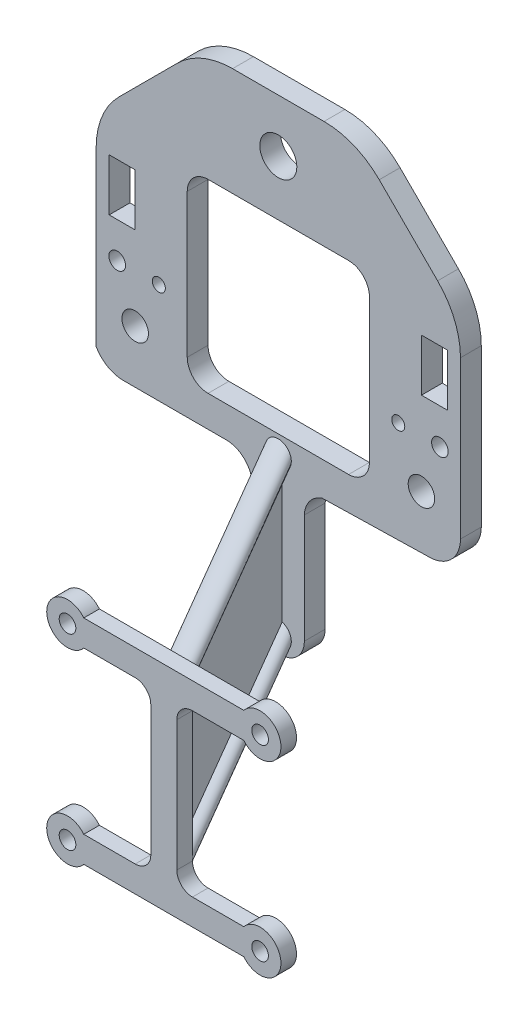
SolidWorks part; units mm, degrees
ref_plane "Спереди" through (0, 0, 0) normal (0, 0, 1) x (1, 0, 0)
ref_plane "Сверху" through (0, 0, 0) normal (0, 1, 0) x (1, 0, 0)
ref_plane "Справа" through (0, 0, 0) normal (1, 0, 0) x (0, 0, -1)
sketch "Model" plane through (0, 0, 0) normal (0, 0, 1) x (1, 0, 0)
  line L0 (-32.5, 1.0025) -> (-27.5, 1.0025)
  line L1 (-27.5, 1.0025) -> (-27.5, 11.0025)
  line L2 (-27.5, 11.0025) -> (-32.5, 11.0025)
  line L3 (-32.5, 11.0025) -> (-32.5, 1.0025)
  line L4 (32.5, 11.0025) -> (27.5, 11.0025)
  line L5 (27.5, 11.0025) -> (27.5, 1.0025)
  line L6 (27.5, 1.0025) -> (32.5, 1.0025)
  line L7 (32.5, 1.0025) -> (32.5, 11.0025)
  line L8 (-8.7868, 37.1928) -> (8.7868, 37.1928)
  line L9 (35, 10.9796) -> (35, -19.1878)
  line L10 (-29.7898, -25.1878) -> (-10, -25.1878)
  line L11 (5, -30.1878) -> (5, -51.1878)
  line L12 (0.5, -55.6878) -> (-0.5, -55.6878)
  line L13 (-5, -51.1878) -> (-5, -30.1878)
  line L14 (8.4254, -25.669) -> (29, -25.1878)
  line L15 (-35, -22.1633) -> (-35, 10.9796)
  line L16 (-15.452, -19.1878) -> (15.452, -19.1878)
  line L17 (-17.5, -3.7682) -> (-17.5, -19.1878) construction
  line L18 (-17.5, -19.1878) -> (-15.452, -19.1878) construction
  line L19 (17.5, 14.8517) -> (17.5, 16.4118) construction
  line L20 (-27.5, 27.0083) -> (27.5, 27.0083) construction
  line L21 (17.5, 16.4118) -> (11.2964, 16.4118) construction
  line L22 (-27.5, 27.0083) -> (-27.5, -15.0033) construction
  line L23 (27.5, 27.0083) -> (27.5, -15.0033) construction
  line L24 (-17.5, -19.1878) -> (17.5, -19.1878)
  line L25 (-17.5, -19.1878) -> (-17.5, 16.4118)
  line L26 (-27.5, -15.0033) -> (27.5, -15.0033) construction
  line L27 (-17.5, 16.4118) -> (17.5, 16.4118)
  line L28 (17.5, -19.1878) -> (17.5, 16.4118)
  line L29 (-10, 16.0025) -> (10, 16.0025) construction
  line L30 (0, -15.0033) -> (0, -40.6878) construction
  line L31 (-5, -40.6878) -> (5, -40.6878) construction
  line L32 (0, -40.6878) -> (0, -51.1878) construction
  line L33 (0, -51.1878) -> (-0.5, -51.1878) construction
  line L34 (0, -51.1878) -> (0.5, -51.1878) construction
  line L35 (-10, -30.1878) -> (-0.5, -30.1878) construction
  line L36 (-0.5, -30.1878) -> (-0.5, -51.1878) construction
  line L37 (-30.6066, 21.5862) -> (-19.3934, 32.7994)
  line L38 (-35, 17.1928) -> (-35, 37.1928) construction
  line L39 (-35, 37.1928) -> (-15, 37.1928) construction
  line L40 (30.6066, 21.5862) -> (19.3934, 32.7994)
  circle A0 centre (-22.955, -5.8427) radius 1.25
  circle A1 centre (23.045, -5.8427) radius 1.25
  circle A2 centre (-30.955, -5.8427) radius 1.6
  circle A3 centre (31.045, -5.8427) radius 1.6
  circle A4 centre (-27.5, -15.0033) radius 2.55
  circle A5 centre (27.5, 27.0083) radius 3.556 construction
  circle A6 centre (-27.5, 27.0083) radius 3.556 construction
  circle A7 centre (27.5, -15.0033) radius 2.55
  circle A8 centre (0, 27.0083) radius 3.556
  arc A9 (35, 10.9796) -> (30.6066, 21.5862) centre (20, 10.9796) ccw
  arc A10 (-35, 10.9796) -> (-30.6066, 21.5862) centre (-20, 10.9796) cw
  arc A11 (19.3934, 32.7994) -> (8.7868, 37.1928) centre (8.7868, 22.1928) ccw
  arc A12 (-19.3934, 32.7994) -> (-8.7868, 37.1928) centre (-8.7868, 22.1928) cw
  arc A104 (29, -25.1878) -> (35, -19.1878) centre (29, -19.1878) ccw
  arc A105 (8.4254, -25.669) -> (5, -30.1878) centre (9.9948, -30.4163) ccw
  arc A106 (0.5, -55.6878) -> (5, -51.1878) centre (0.5, -51.1878) ccw
  arc A107 (-5, -51.1878) -> (-0.5, -55.6878) centre (-0.5, -51.1878) ccw
  arc A108 (-5, -30.1878) -> (-10, -25.1878) centre (-10, -30.1878) ccw
  arc A109 (-35, -22.1633) -> (-29.7898, -25.1878) centre (-29.7898, -19.1878) ccw
  point P29 (6.0102, -27.3959)
  point P38 (35, 17.1928)
  point P44 (15, 37.1928)
  dimension "D1" = 7.112
  dimension "D2" = 7.112
  dimension "D6" = 5
  dimension "D7" = 4.5
  dimension "D8" = 4.5
  dimension "D12" = 15
  dimension "D3" = 42.0116
  dimension "D4" = 10
  dimension "D5" = 5
  dimension "D9" = 21
  dimension "D10" = 20
  dimension "D11" = 20
extrude "Бобышка-Вытянуть1" add sketch "Model" along normal blind 4 contours L15 A109 L10 A108 L13 A107 L12 A106 L11 A105 L14 A104 L9 L8 L3 L2 L1 L0 L7 L6 L5 L4 L28 L24 L16 L25 L27 A0 A1 A2 A3 A4 A5 A6 A7 region at (0, 36.0297, 0)
sketch "Эскиз1" plane through (0, 0, 4) normal (0, 0, 1) x (1, 0, 0)
  line L0 (-27.5, -15.0033) -> (27.5, -15.0033) construction
  line L1 (0, -15.0033) -> (0, -22.5033) construction
  line L2 (0, -22.5033) -> (0, -52.5033) construction
  line L3 (0, -37.5033) -> (0.75, -37.5033) construction
  line L5 (0.75, -50.1185) -> (0.75, -24.8882)
  line L6 (-0.75, -50.1185) -> (-0.75, -24.8882)
  arc A0 (0.75, -24.8882) -> (-0.75, -24.8882) centre (0, -22.5033) ccw
  arc A1 (0.75, -50.1185) -> (-0.75, -50.1185) centre (0, -52.5033) cw
  point P14 (-0.75, -37.5033)
  dimension "D3" = 5
  dimension "D1" = 7.5
  dimension "D2" = 30
  dimension "D4" = 0.75
sketch "Эскиз2" plane through (0, 0, 0) normal (1, 0, 0) x (0, 0, -1)
  line L0 (-4, -22.5033) -> (-4, -49.0033) construction
  line L1 (-4, -49.0033) -> (-23, -49.0033) construction
  line L2 (-4, -22.5033) -> (-23, -49.0033) construction
  dimension "D1" = 26.5
  dimension "D2" = 19
sketch "Эскиз3" plane through (0, 0, 0) normal (1, 0, 0) x (0, 0, -1)
  line L0 (-4, -22.5033) -> (-23, -49.0033) construction
extrude "Бобышка-Вытянуть2" add sketch "Эскиз1" along direction (0, -0.8127, 0.5827) on the side of the normal up to vertex (19 mm away) up to point (0, -49.0033, 23)
sketch "Эскиз4" plane through (0, 0, 23) normal (0, 0, 1) x (1, 0, 0)
  line L0 (0, -49.0033) -> (0, -79.0033) construction
  line L1 (0, -49.0033) -> (18.5, -49.0033) construction
  line L2 (9.25, -49.0033) -> (9.25, -51.5033) construction
  line L3 (15.3775, -51.5033) -> (5.5, -51.5033)
  line L4 (15.3775, -46.5033) -> (-15.3775, -46.5033)
  line L5 (0, -64.0033) -> (2.5, -64.0033) construction
  line L6 (2.5, -54.5033) -> (2.5, -64.0033)
  line L7 (-2.5, -54.5033) -> (-2.5, -64.0033)
  line L8 (-15.3775, -51.5033) -> (-5.5, -51.5033)
  line L9 (0, -67.0033) -> (7.4707, -67.0033) construction
  line L10 (7.4707, -67.0033) -> (7.4707, -49.0033) construction
  line L11 (-15.3775, -82.5033) -> (-5.5, -82.5033)
  line L12 (15.3775, -82.5033) -> (5.5, -82.5033)
  line L13 (15.3775, -87.5033) -> (-15.3775, -87.5033)
  line L14 (-2.5, -64.0033) -> (-2.5, -79.5033)
  line L15 (2.5, -64.0033) -> (2.5, -79.5033)
  arc A0 (15.3775, -51.5033) -> (15.3775, -46.5033) centre (18.5, -49.0033) ccw
  circle A1 centre (18.5, -49.0033) radius 1.6
  arc A2 (2.5, -54.5033) -> (5.5, -51.5033) centre (5.5, -54.5033) cw
  arc A3 (-2.5, -54.5033) -> (-5.5, -51.5033) centre (-5.5, -54.5033) ccw
  circle A4 centre (-18.5, -49.0033) radius 1.6
  arc A5 (-15.3775, -51.5033) -> (-15.3775, -46.5033) centre (-18.5, -49.0033) cw
  circle A6 centre (-18.5, -85.0033) radius 1.6
  arc A7 (-2.5, -79.5033) -> (-5.5, -82.5033) centre (-5.5, -79.5033) cw
  arc A8 (2.5, -79.5033) -> (5.5, -82.5033) centre (5.5, -79.5033) ccw
  circle A9 centre (18.5, -85.0033) radius 1.6
  arc A10 (15.3775, -82.5033) -> (15.3775, -87.5033) centre (18.5, -85.0033) cw
  arc A11 (-15.3775, -82.5033) -> (-15.3775, -87.5033) centre (-18.5, -85.0033) ccw
  point P25 (0, -46.5033)
  dimension "D2" = 8
  dimension "D3" = 3.2
  dimension "D6" = 3
  dimension "D1" = 18.5
  dimension "D4" = 2.5
  dimension "D5" = 2.5
  dimension "D7" = 18
extrude "Бобышка-Вытянуть3" add sketch "Эскиз4" along normal blind 3
fillet "Скругление1" radius 4 4 edges at (-17.5, 16.4118, 2) (17.5, 16.4118, 2) (17.5, -19.1878, 2) (-17.5, -19.1878, 2)
